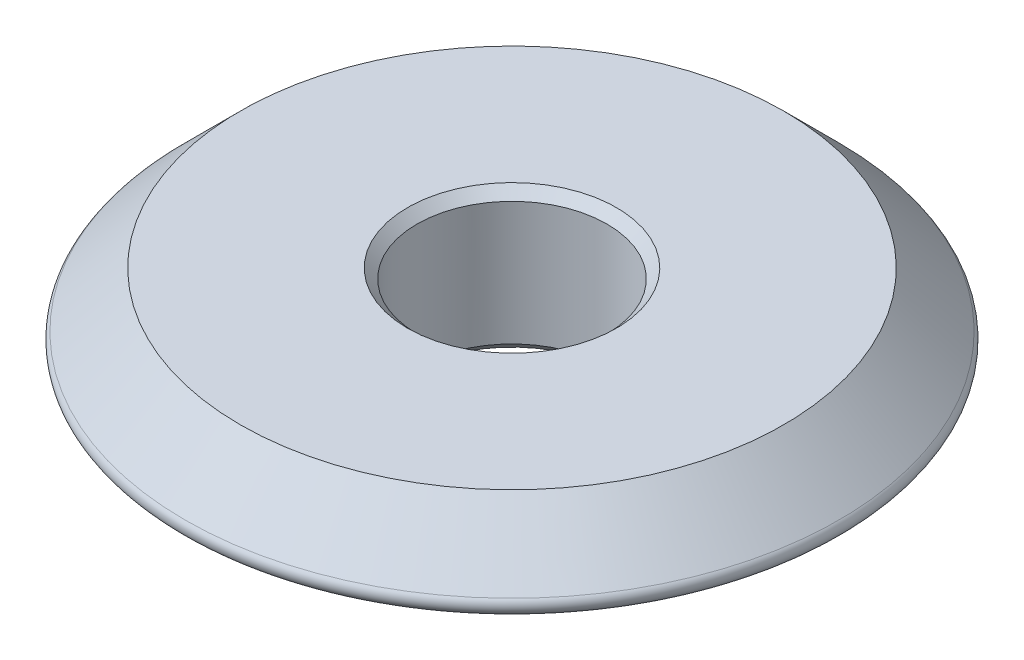
SolidWorks part; units mm, degrees
material "Markforged"
ref_plane "Front Plane" through (0, 0, 0) normal (0, 0, 1) x (1, 0, 0)
ref_plane "Top Plane" through (0, 0, 0) normal (0, 1, 0) x (1, 0, 0)
ref_plane "Right Plane" through (0, 0, 0) normal (1, 0, 0) x (0, 0, -1)
other "Bounding Box"
ref_plane "Default Plane" through (-8.9266, -12.7485, 0) normal (-0.1736, 0.9848, 0) x (0.9848, 0.1736, 0)
sketch "Sketch1" plane through (0, 0, 0) normal (1, 0, 0) x (0, 0, -1)
  line L0 (0, 0) -> (0, 8.0505) construction
  line L2 (2.54, 1.905) -> (7.2644, 1.905)
  line L3 (7.2644, 1.905) -> (9.1694, 0)
  line L4 (9.1694, 0) -> (4.2749, 0)
  line L5 (4.2749, 0) -> (3.175, -1.905)
  line L6 (3.175, -1.905) -> (2.54, -1.905)
  line L8 (2.54, -1.905) -> (2.54, 1.905)
  point P1 (3.175, 0)
  point P6 (4.4538, 0)
  dimension "D1" = 7.2644
  dimension "D2" = 45
  dimension "D3" = 1.905
  dimension "D4" = 3.81
  dimension "D5" = 6.35
  dimension "D6" = 5.08
  dimension "D7" = 30
revolve "Revolve1" add sketch "Sketch1" angle 360 about L0
sketch "Sketch2" plane through (0, 0, 0) normal (0, -1, 0) x (1, 0, 0)
  line L0 (-7.9729, 4.5289) -> (7.9729, 4.5289) construction
  line L1 (0, 4.2749) -> (0, 4.5289) construction
  circle A0 centre (0, 0) radius 9.1694 construction
  circle A1 centre (0, 0) radius 4.2749 construction
  text T0 "<b>In</b>" font "Comic Sans MS" height 3.81
  dimension "D1" = 0.254
extrude "Cut-Extrude1" cut sketch "Sketch2" against normal blind 0.254
fillet "Fillet1" radius 0.254 1 edges at (0, 0, -9.1694)
chamfer "Chamfer1" distance 0.254 angle 45 2 edges at (0, 1.905, -2.54) (0, -1.905, -2.54)
